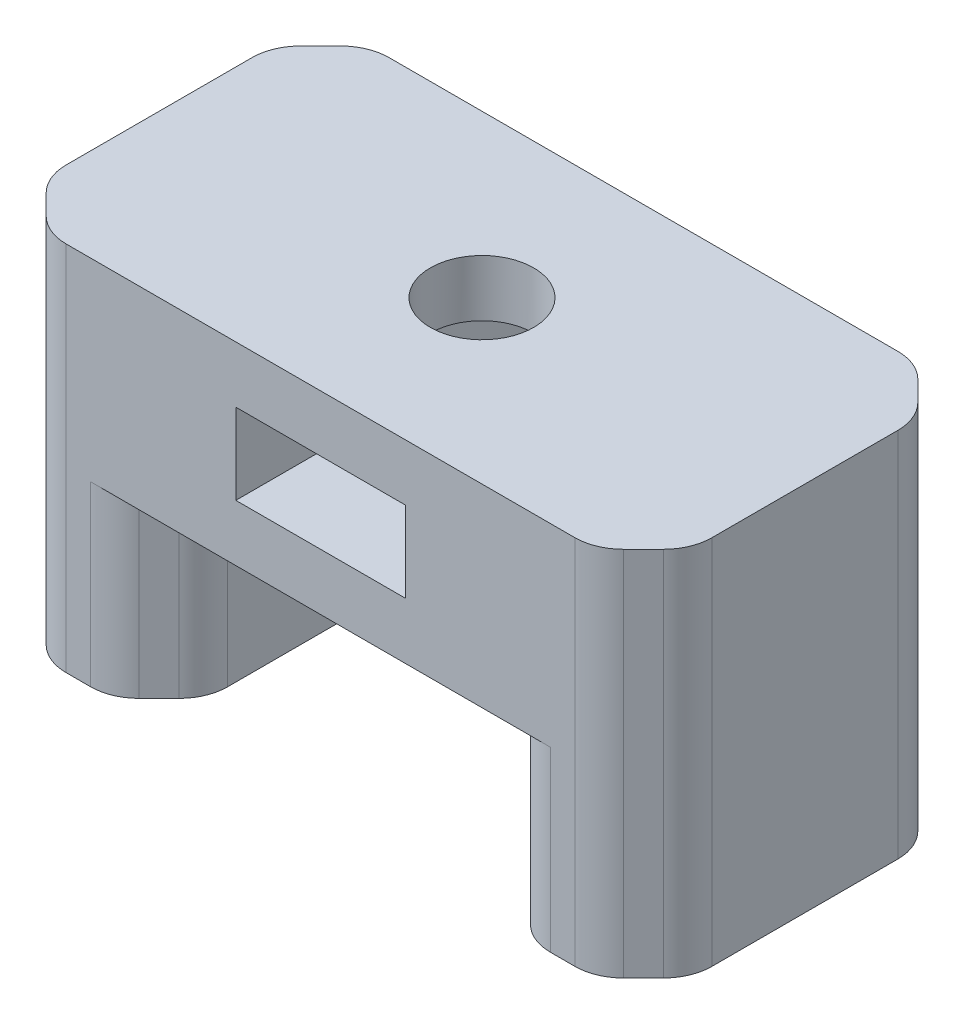
SolidWorks part; units mm, degrees
ref_plane "Plan de face" through (0, 0, 0) normal (0, 0, 1) x (1, 0, 0)
ref_plane "Plan de dessus" through (0, 0, 0) normal (0, 1, 0) x (1, 0, 0)
ref_plane "Plan de droite" through (0, 0, 0) normal (1, 0, 0) x (0, 0, -1)
sketch "Esquisse1" plane through (0, 0, 0) normal (0, 1, 0) x (1, 0, 0)
  line L0 (-20, 10) -> (-20, -10)
  line L1 (-20, 10) -> (-10, 10)
  line L2 (10, 0) -> (-10, 0) construction
  line L3 (-10, -10) -> (-20, -10)
  line L4 (-10, -10) -> (-10, 10)
  line L5 (-10, 10) -> (-20, 10)
  line L7 (-20, -10) -> (-10, -10)
  line L8 (-10, -10) -> (-10, 10)
  line L15 (0, -55) -> (0, 55) construction
  line L16 (10, -10) -> (10, 10)
  line L17 (20, -10) -> (10, -10)
  line L18 (10, 10) -> (20, 10)
  line L19 (10, -10) -> (10, 10)
  line L20 (10, -10) -> (20, -10)
  line L21 (20, 10) -> (10, 10)
  line L22 (20, 10) -> (20, -10)
  line L23 (-15, 0) -> (-10, 0) construction
  circle A0 centre (-15, 0) radius 2.75
  circle A2 centre (15, 0) radius 2.75
  circle A3 centre (-15, 0) radius 3.5
  circle A4 centre (15, 0) radius 3.5
  point P8 (0, 0)
  dimension "D1" = 20
  dimension "D5" = 5.5
  dimension "D7" = 5.5
  dimension "D2" = 10
  dimension "D3" = 10
  dimension "D4" = 5
  dimension "D6" = 15
extrude "Boss.-Extru.1" add sketch "Esquisse1" along normal blind 11 contours L3 L4 L1 L0 A0 | L22 L18 L16 L17 A2 | A2 | A0 | A3 A0 | A4 A2 region at (-15, 0, -9.7764) region at (10.2236, 0, 0) region at (-15, 0, 0) region at (15, 0, 0) region at (-18.401, 0, 0) region at (11.599, 0, 0)
sketch "Esquisse3" plane through (0, 11, 0) normal (0, 1, 0) x (1, 0, 0)
  line L0 (-20, -10) -> (20, -10)
  line L1 (20, -10) -> (20, 10)
  line L3 (20, 10) -> (-20, 10)
  line L4 (-20, 10) -> (-20, -10)
  line M1 (-20, -10) -> (-10, -10)
  line M2 (-10, -10) -> (-10, 10)
  line M3 (-10, 10) -> (-20, 10)
  line M4 (-20, 10) -> (-20, -10)
extrude "Boss.-Extru.2" add sketch "Esquisse3" along normal blind 12 contours M4 M1 M2 M3 | L1 L3 L0 M2 | L4 L0 L1 L3 region at (-15, 11, 0) region at (5, 11, 0)
sketch "Esquisse4" plane through (0, 23, 0) normal (0, 1, 0) x (1, 0, 0)
  circle A0 centre (0, 0) radius 3.2
extrude "Enlèv. mat.-Extru.1" cut sketch "Esquisse4" against normal up to next
extrude "Enlèv. mat.-Extru.3" cut sketch "Esquisse1<3>" along normal blind 15 contours A0 | A2 region at (-15, 0, 0) region at (15, 0, 0)
sketch "Esquisse1<3>" plane through (0, 0, 0) normal (0, 1, 0) x (1, 0, 0) same geometry as "Esquisse1"
extrude "Enlèv. mat.-Extru.4" cut sketch "Esquisse1<4>" along normal blind 1 contours A3 A0 | A4 A2 region at (-18.401, 0, 0) region at (11.599, 0, 0)
sketch "Esquisse1<4>" plane through (0, 0, 0) normal (0, 1, 0) x (1, 0, 0) same geometry as "Esquisse1"
chamfer "Chanfrein1" distance 3 angle 45 8 edges at (10, 5.5, -10) (20, 11.5, -10) (10, 5.5, 10) (-10, 5.5, -10) (-10, 5.5, 10) (20, 11.5, 10) (-20, 11.5, -10) (-20, 11.5, 10)
fillet "Congé1" radius 3 16 edges at (-10, 5.5, -7) (-13, 5.5, -10) (10, 5.5, -7) (13, 5.5, -10) (13, 5.5, 10) (17, 11.5, 10) (20, 11.5, 7) (20, 11.5, -7) (17, 11.5, -10) (-17, 11.5, -10) (-20, 11.5, -7) (-20, 11.5, 7) (-17, 11.5, 10) (-10, 5.5, 7) (-13, 5.5, 10) (10, 5.5, 7)
ref_plane "Plan1" through (0, 14.5, 0) normal (0, -1, 0) x (-1, 0, 0)
sketch "Esquisse6" plane through (0, 14.5, 0) normal (0, -1, 0) x (-1, 0, 0)
  line L0 (14.2426, -10) -> (-14.2426, -10) construction
  line L7 (-5.25, 10) -> (5.25, 10)
  line L8 (-5.25, 10) -> (-5.25, -10)
  line L10 (-5.25, -10) -> (5.25, -10)
  line L11 (5.25, 10) -> (5.25, -10)
  line L12 (-5.25, 10) -> (5.25, -10) construction
  line L13 (-5.25, -10) -> (5.25, 10) construction
  point P0 (0, 0)
  point P1 (0, 0)
  dimension "D1" = 10.5
extrude "Enlèv. mat.-Extru.5" cut sketch "Esquisse6" against normal blind 5
